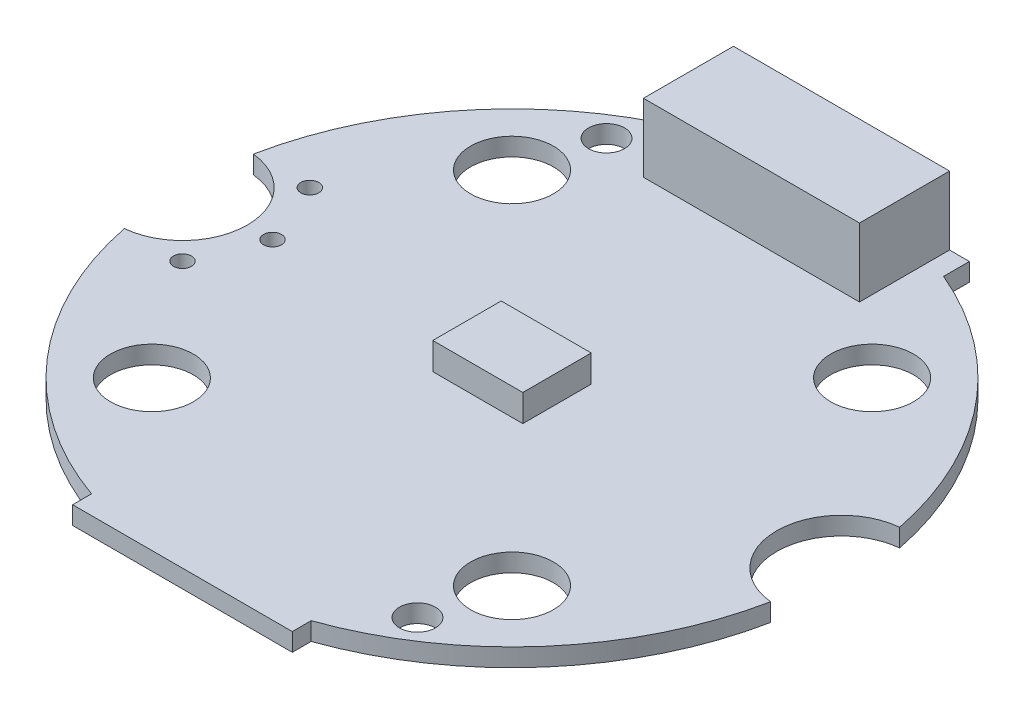
SolidWorks part; units mm, degrees
ref_plane "Front plane" through (0, 0, 0) normal (0, 0, 1) x (1, 0, 0)
ref_plane "Top plane" through (0, 0, 0) normal (0, 1, 0) x (1, 0, 0)
ref_plane "Right plane" through (0, 0, 0) normal (1, 0, 0) x (0, 0, -1)
ref_axis "Axis X" through (0, 0, 0) along (1, 0, 0)
ref_axis "Axis Y" through (0, 0, 0) along (0, 1, 0)
ref_axis "Axis Z" through (0, 0, 0) along (0, 0, 1)
sketch "Sketch1" plane through (0, 0, 0) normal (0, 1, 0) x (1, 0, 0)
  line L0 (0, 0) -> (0, 18.3) construction
  line L2 (-18.3, 0) -> (18.3, 0) construction
  line L3 (-7.1, 18.3) -> (-7.1, 16.8665)
  line L4 (-7.1, 18.3) -> (7.1, 18.3)
  line L5 (7.1, 18.3) -> (7.1, 16.8665)
  line L6 (6.1, -17.2534) -> (6.1, -18.3)
  line L7 (6.1, -18.3) -> (-6.1, -18.3)
  line L8 (-6.1, -18.3) -> (-6.1, -17.2534)
  line L9 (10, 10) -> (-10, 10) construction
  line L10 (10, 10) -> (10, -10) construction
  line L11 (10, -10) -> (-10, -10) construction
  line L12 (-10, 10) -> (-10, -10) construction
  line L13 (10, 10) -> (-10, -10) construction
  line L14 (10, -10) -> (-10, 10) construction
  arc A0 (-17.9459, -3.5825) -> (-6.1, -17.2534) centre (0, 0) ccw
  arc A1 (-17.9459, -3.5825) -> (-17.9459, 3.5825) centre (-18.3, 0) ccw
  arc A2 (17.9459, 3.5825) -> (17.9459, -3.5825) centre (18.3, 0) ccw
  arc A3 (-17.9459, 3.5825) -> (-17.9459, -3.5825) centre (-18.3, 0) ccw construction
  arc A4 (-17.9459, 3.5825) -> (-17.9459, -3.5825) centre (0, 0) ccw construction
  arc A5 (17.9459, -3.5825) -> (17.9459, 3.5825) centre (18.3, 0) ccw construction
  arc A6 (17.9459, 3.5825) -> (7.1, 16.8665) centre (0, 0) ccw
  arc A7 (17.9459, -3.5825) -> (17.9459, 3.5825) centre (0, 0) ccw construction
  arc A12 (-7.1, 16.8665) -> (-17.9459, 3.5825) centre (0, 0) ccw
  arc A13 (0, 18.3) -> (-7.1, 16.8665) centre (0, 0) ccw construction
  arc A14 (7.1, 16.8665) -> (0, 18.3) centre (0, 0) ccw construction
  arc A17 (6.1, -17.2534) -> (17.9459, -3.5825) centre (0, 0) ccw
  arc A18 (-6.1, -17.2534) -> (0, -18.3) centre (0, 0) ccw construction
  arc A19 (0, -18.3) -> (6.1, -17.2534) centre (0, 0) ccw construction
  circle A20 centre (-10, 10) radius 2.3
  circle A21 centre (10, 10) radius 2.3
  circle A22 centre (10, -10) radius 2.3
  circle A23 centre (-10, -10) radius 2.3
  point P32 (0, 0)
  dimension "D1" = 36.6
  dimension "D2" = 7.2
  dimension "D3" = 7.2
  dimension "D6" = 4.6
  dimension "D8" = 14.2
  dimension "D9" = 12.2
  dimension "D4" = 20
  dimension "D5" = 20
  dimension "D7" = 4
extrude "Extrude1" add sketch "Sketch1" along normal blind 1
sketch "Sketch2" plane through (0, 1, 0) normal (0, 1, 0) x (1, 0, 0)
  line L0 (7.1, 18.3) -> (-7.1, 18.3) construction
  line L1 (-6, 18.3) -> (6, 18.3)
  line L2 (-6, 18.3) -> (-6, 13.3)
  line L3 (-6, 13.3) -> (6, 13.3)
  line L4 (6, 18.3) -> (6, 13.3)
  line L5 (0, 18.3) -> (0, 0) construction
  dimension "D1" = 12
  dimension "D2" = 5
extrude "Extrude2" add sketch "Sketch2" along normal blind 3.8
sketch "Sketch3" plane through (0, 1, 0) normal (0, 1, 0) x (1, 0, 0)
  line L1 (-2.5, 1.9) -> (2.5, 1.9)
  line L2 (-2.5, 1.9) -> (-2.5, -1.9)
  line L3 (-2.5, -1.9) -> (2.5, -1.9)
  line L4 (2.5, 1.9) -> (2.5, -1.9)
  line L5 (-2.5, 1.9) -> (2.5, -1.9) construction
  line L6 (-2.5, -1.9) -> (2.5, 1.9) construction
  point P0 (0, 0)
  dimension "D1" = 5
  dimension "D2" = 3.8
extrude "Extrude3" add sketch "Sketch3" along normal blind 1.5
sketch "Sketch4" plane through (0, 0, 0) normal (0, -1, 0) x (1, 0, 0)
  line L0 (0, 0) -> (0, 18.3) construction
  line L1 (-6.1, 18.3) -> (6.1, 18.3) construction
  line L3 (-3, 11.8) -> (3, 11.8)
  line L4 (-3, 11.8) -> (-3, 4.7)
  line L5 (-3, 4.7) -> (3, 4.7)
  line L6 (3, 11.8) -> (3, 4.7)
  line L7 (-3, 11.8) -> (3, 4.7) construction
  line L8 (-3, 4.7) -> (3, 11.8) construction
  point P5 (0, 8.25)
  dimension "D1" = 6
  dimension "D2" = 7.1
  dimension "D3" = 4.7
extrude "Extrude4" add sketch "Sketch4" along normal blind 2
sketch "Sketch5" plane through (0, 1, 0) normal (0, 1, 0) x (1, 0, 0)
  line L1 (8.9, 14.15) -> (-8.9, 14.15) construction
  line L2 (8.9, 14.15) -> (8.9, -14.15) construction
  line L3 (8.9, -14.15) -> (-8.9, -14.15) construction
  line L4 (-8.9, 14.15) -> (-8.9, -14.15) construction
  line L5 (8.9, 14.15) -> (-8.9, -14.15) construction
  line L6 (8.9, -14.15) -> (-8.9, 14.15) construction
  circle A0 centre (-8.9, 14.15) radius 1
  circle A1 centre (8.9, -14.15) radius 1
  point P0 (0, 0)
  dimension "D3" = 2
  dimension "D4" = 2
  dimension "D1" = 28.3
  dimension "D2" = 17.8
extrude "Extrude5" cut sketch "Sketch5" against normal through all both and the other way through all contours A1 | A0
sketch "Sketch6" plane through (0, 0, 0) normal (0, -1, 0) x (1, 0, 0)
  line L0 (-18.3, 0) -> (-14.7645, 3.5355) construction
  line L1 (-18.3, 0) -> (-14.7645, -3.5355) construction
  line L2 (-18.3, 0) -> (-13.3, 0) construction
  circle A0 centre (-18.3, 0) radius 5 construction
  circle A1 centre (-13.3, 0) radius 0.5
  circle A2 centre (-14.7645, 3.5355) radius 0.5
  circle A3 centre (-14.7645, -3.5355) radius 0.5
  dimension "D1" = 10
  dimension "D2" = 1
  dimension "D3" = 1
  dimension "D4" = 1
  dimension "D5" = 45
  dimension "D6" = 45
extrude "Extrude6" cut sketch "Sketch6" against normal through all
equation "\"D3@Sketch1\"=\"D2@Sketch1\""
equation "\"l1\"=28.3"
equation "\"D1@Sketch5\"=\"l1\""
equation "\"l2\"=17.8"
equation "\"D2@Sketch5\"=\"l2\""
equation "\"D4@Sketch5\"=\"D3@Sketch5\""
equation "\"D5@Sketch1\"=\"D4@Sketch1\""
equation "\"D3@Sketch6\"=\"D2@Sketch6\""
equation "\"D4@Sketch6\"=\"D2@Sketch6\""
